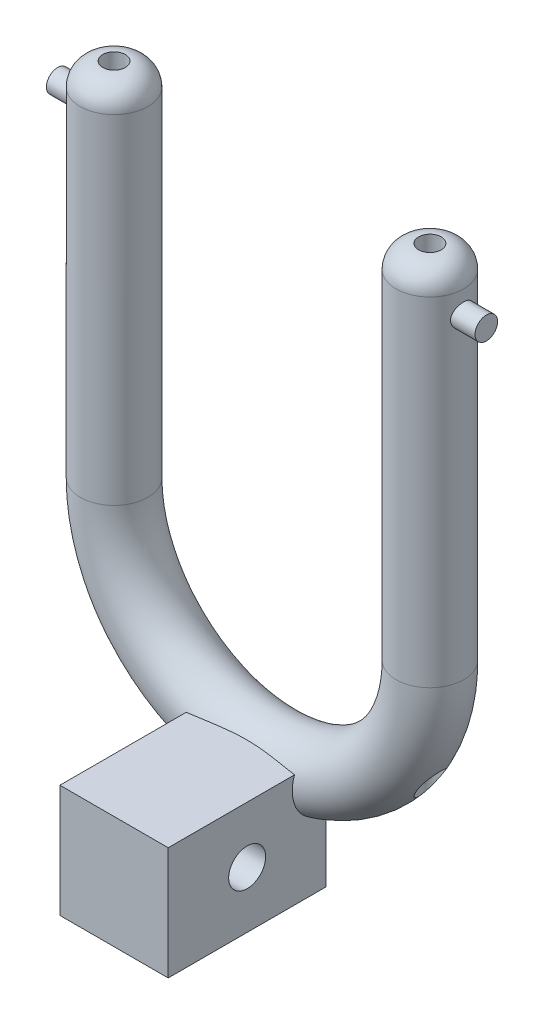
SolidWorks part; units mm, degrees
ref_plane "Front Plane" through (0, 0, 0) normal (0, 0, 1) x (1, 0, 0)
ref_plane "Top Plane" through (0, 0, 0) normal (0, 1, 0) x (1, 0, 0)
ref_plane "Right Plane" through (0, 0, 0) normal (1, 0, 0) x (0, 0, -1)
sketch "Sketch1" plane through (0, 0, 0) normal (0, 0, 1) x (1, 0, 0)
  line L0 (-56.4924, 0) -> (-91.4924, 0) construction
  line L1 (-91.4924, 0) -> (-21.4924, 0) construction
  line L2 (-91.4924, 0) -> (-91.4924, 80)
  line L3 (-21.4924, 0) -> (-21.4924, 80)
  arc A1 (-91.4924, 0) -> (-21.4924, 0) centre (-56.4924, 0) ccw
  point P0 (-56.4924, 0)
sweep "Sweep1" add path "Sketch1" circular profile diameter 15 parameters "D3"=15
sketch "Sketch7" plane through (0, 0, 0) normal (0, 0, 1) x (1, 0, 0)
  line L1 (-68.4924, -55) -> (-44.4924, -55)
  line L2 (-68.4924, -55) -> (-68.4924, -30)
  line L3 (-68.4924, -30) -> (-44.4924, -30)
  line L4 (-44.4924, -55) -> (-44.4924, -30)
  line L5 (-68.4924, -55) -> (-44.4924, -30) construction
  line L6 (-68.4924, -30) -> (-44.4924, -55) construction
  arc A0 (-98.9924, 0) -> (-13.9924, 0) centre (-56.4924, 0) ccw construction
  point P0 (-56.4924, -42.5)
extrude "Boss-Extrude1" add sketch "Sketch7" along normal blind 35
sketch "Sketch8" plane through (-44.4924, 0, 0) normal (1, 0, 0) x (0, 0, -1)
  line L0 (-35, -42.5) -> (0, -42.5) construction
  line L1 (-35, -55) -> (-35, -30) construction
  line L2 (0, 46.75) -> (0, -46.75) construction
  line L3 (-17.5, -55) -> (-17.5, -30) construction
  line L4 (-35, -30) -> (-7.0014, -30) construction
  line L5 (-35, -55) -> (0, -55) construction
  circle A0 centre (-17.5, -42.5) radius 4.1
extrude "Cut-Extrude1" cut sketch "Sketch8" against normal through all
sketch "Sketch9" plane through (0, 0, 0) normal (0, 1, 0) x (1, 0, 0)
  circle A0 centre (-91.4924, 0) radius 2.5
  circle A1 centre (-21.4924, 0) radius 2.5
extrude "Cut-Extrude2" cut sketch "Sketch9" against normal through all both and the other way through all
ref_plane "Plane1" through (-56.4924, 0, 0) normal (1, 0, 0) x (0, 0, -1)
sketch "Sketch11" plane through (-56.4924, 0, 0) normal (1, 0, 0) x (0, 0, -1)
  line L0 (0, 80) -> (0, 70) construction
  line L1 (7.5, 80) -> (-7.5, 80) construction
  line L2 (0, 46.75) -> (0, -46.75) construction
  circle A0 centre (0, 70) radius 2.5
extrude "Boss-Extrude2" add sketch "Sketch11" along normal blind 6 from offset 41.5 separate body
extrude "Boss-Extrude3" add sketch "Sketch11<2>" against normal blind 6 from offset 41.5 separate body offset against normal yes
sketch "Sketch11<2>" plane through (-56.4924, 0, 0) normal (1, 0, 0) x (0, 0, -1) same geometry as "Sketch11"
fillet "Fillet1" radius 5 2 edges at (-21.4924, 80, -7.5) (-91.4924, 80, -7.5)
